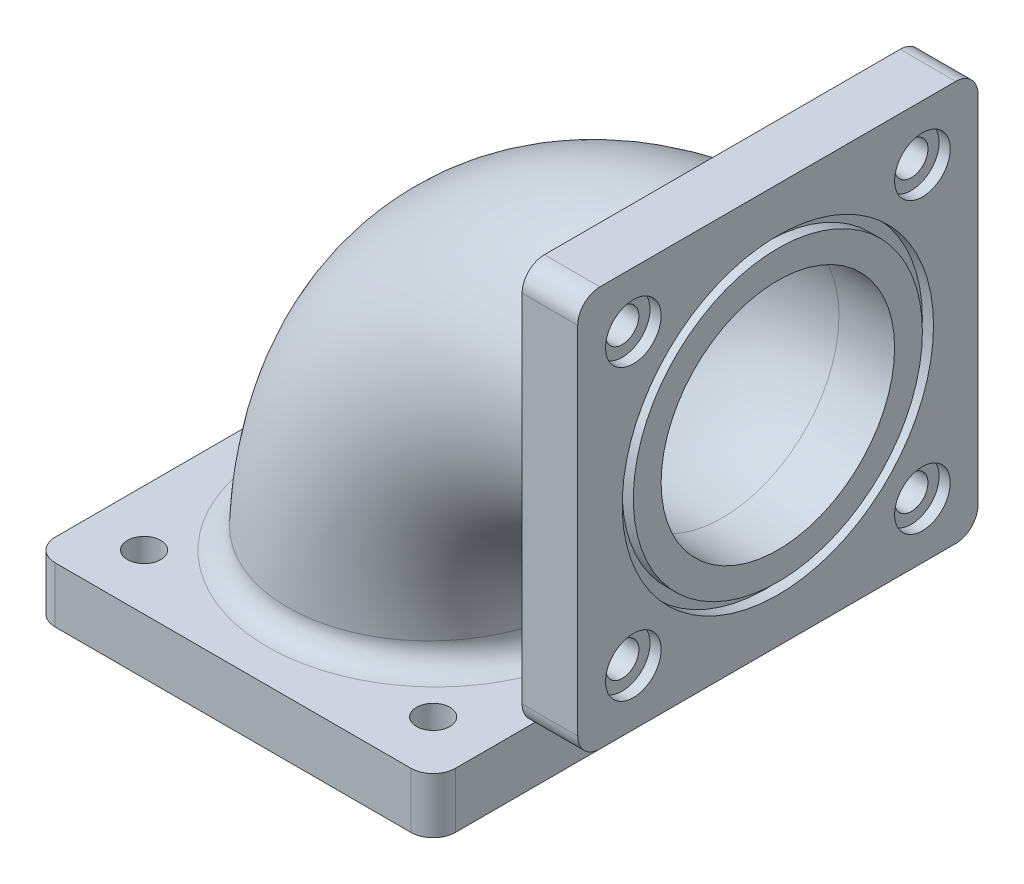
SolidWorks part; units mm, degrees
ref_plane "Front Plane" through (0, 0, 0) normal (0, 0, 1) x (1, 0, 0)
ref_plane "Top Plane" through (0, 0, 0) normal (0, 1, 0) x (1, 0, 0)
ref_plane "Right Plane" through (0, 0, 0) normal (1, 0, 0) x (0, 0, -1)
sketch "Sketch6" plane through (0, 0, 0) normal (1, 0, 0) x (0, 0, -1)
  circle A0 centre (0, 26) radius 13
  circle A1 centre (0, 26) radius 10.5
  point P3 (0, 0)
  dimension "D1" = 26
  dimension "D2" = 21
  dimension "D3" = 26
ref_axis "Axis1" through (0, 0, -14.3) along (0, 0, 1)
revolve "Revolve1" add sketch "Sketch6" angle 90 about axis through (0, 0, -14.3) along (0, 0, 1)
extrude "Boss-Extrude1" add sketch "Sketch6<2>" along normal blind 5
sketch "Sketch6<2>" plane through (0, 0, 0) normal (1, 0, 0) x (0, 0, -1) same geometry as "Sketch6"
sketch "Sketch9" plane through (5, 0, 0) normal (1, 0, 0) x (0, 0, -1)
  line L1 (-18, 8) -> (18, 8)
  line L2 (-18, 8) -> (-18, 44)
  line L3 (-18, 44) -> (18, 44)
  line L4 (18, 8) -> (18, 44)
  line L5 (-18, 8) -> (18, 44) construction
  line L6 (-18, 44) -> (18, 8) construction
  point P0 (0, 26)
  point P5 (0, 0)
  dimension "D1" = 26
  dimension "D2" = 36
extrude "Boss-Extrude2" add sketch "Sketch9" against normal blind 5
sketch "Sketch10" plane through (5, 0, 0) normal (1, 0, 0) x (0, 0, -1)
  circle A0 centre (0, 26) radius 10.5
  circle A1 centre (0, 26) radius 10.5 construction
  dimension "D1" = 21
extrude "Cut-Extrude1" cut sketch "Sketch10" against normal blind 5 contours A0
sketch "Sketch11" plane through (5, 0, 0) normal (1, 0, 0) x (0, 0, -1)
  circle A0 centre (0, 26) radius 13
  circle A1 centre (0, 26) radius 14
  dimension "D1" = 26
  dimension "D2" = 28
extrude "Cut-Extrude2" cut sketch "Sketch11" against normal blind 1
hole_wizard "Hole1" positions "3DSketch5" profile "Sketch17" legacy end condition up to next
sketch3d "3DSketch5"
  line L0 (5, 44, -18) -> (5, 44, 18) construction
  line L1 (5, 44, 18) -> (5, 8, 18) construction
  point P0 (5, 39, 13)
  point P3 (5, 39.8547, 13.9894)
  dimension "D1" = 5
  dimension "D2" = 5
sketch "Sketch17" plane through (5, 39, 13) normal (0, 1, 0) x (0, 0, -1)
  line L0 (0, 0) -> (0, 5)
  line L1 (0, 5) -> (1.5, 5)
  line L2 (1.5, 5) -> (1.5, 1)
  line L3 (1.5, 1) -> (2.5, 1)
  line L4 (2.5, 1) -> (2.5, 0)
  line L5 (2.5, 0) -> (0, 0)
  line L6 (0, 110) -> (0, -10) construction
  dimension "Diameter" = 3
  dimension "Depth" = 5
  dimension "C-Bore Diameter" = 5
  dimension "C-Bore Depth" = 1
pattern_linear "LPattern1" count 2 spacing 26 along (0, 0, -1) count 2 spacing 26 along (0, -1, 0) of "Hole1"
fillet "Fillet1" radius 2 5 edges at (0, 26, -13) (2.5, 8, -18) (2.5, 8, 18) (2.5, 44, 18) (2.5, 44, -18)
ref_plane "Plane1" through (0, 0, 0) normal (0.7071, 0.7071, 0) x (0.7071, -0.7071, 0)
mirror "Mirror1" about plane through (0, 0, 0) normal (0.7071, 0.7071, 0) of "Fillet1", "LPattern1", "Hole1", "Cut-Extrude2", "Cut-Extrude1", "Boss-Extrude1", "Boss-Extrude2"
